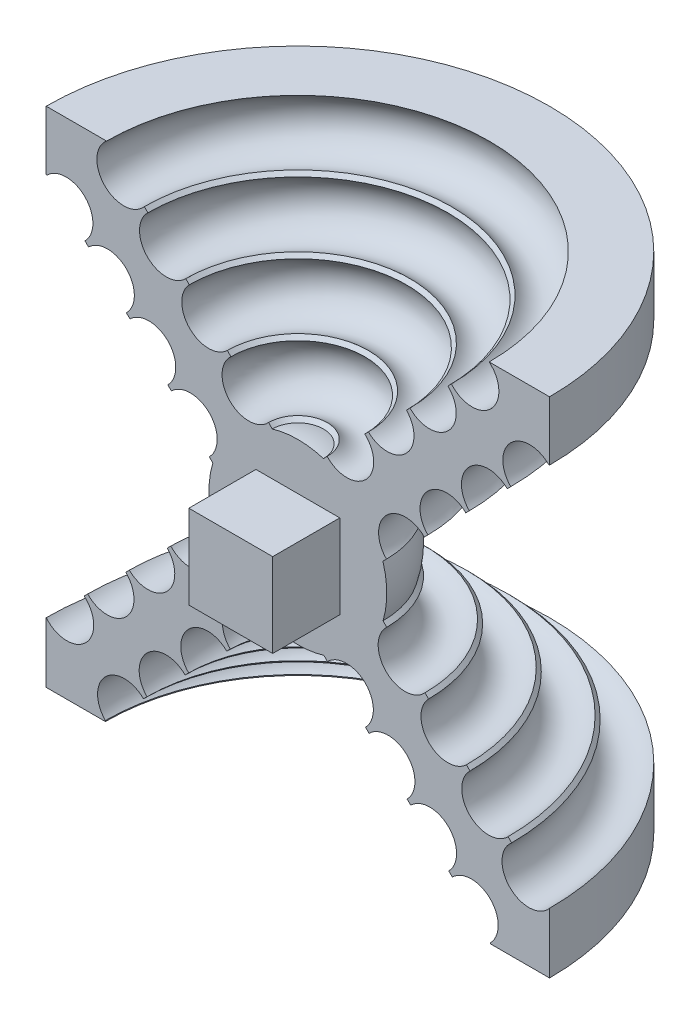
SolidWorks part; units mm, degrees
ref_plane "Front Plane" through (0, 0, 0) normal (0, 0, 1) x (1, 0, 0)
ref_plane "Top Plane" through (0, 0, 0) normal (0, 1, 0) x (1, 0, 0)
ref_plane "Right Plane" through (0, 0, 0) normal (1, 0, 0) x (0, 0, -1)
sketch "Sketch1" plane through (0, 0, 0) normal (0, 0, 1) x (1, 0, 0)
  line L42 (-19.05, 14.5706) -> (-19.05, 19.05) construction
  line L43 (-19.05, 19.05) -> (-14.4798, 19.05) construction
  line L46 (-18.9806, 14.5706) -> (-19.05, 14.5706)
  line L51 (1.9692, 6.4365) -> (2.2383, 6.7071)
  line L52 (6.4458, 1.9385) -> (6.727, 2.2183)
  line L66 (-6.4365, 1.9692) -> (-6.7071, 2.2383)
  line L67 (5.1188, 9.5739) -> (5.3889, 9.8426)
  line L68 (9.6188, 5.068) -> (9.8917, 5.3396)
  line L69 (-1.9385, 6.4458) -> (-2.2183, 6.727)
  line L70 (8.2694, 12.7095) -> (8.5395, 12.9782)
  line L71 (0, 19.05) -> (0, 0) construction
  line L72 (12.7597, 8.2194) -> (13.0295, 8.488)
  line L73 (11.42, 15.845) -> (11.6901, 16.1138)
  line L74 (15.91, 11.3547) -> (16.1804, 11.6238)
  line L75 (14.5706, 19.05) -> (19.05, 19.05)
  line L76 (19.05, 19.05) -> (19.05, 14.4798)
  line L77 (6.4365, -1.9692) -> (6.7071, -2.2383)
  line L78 (1.9385, -6.4458) -> (2.2183, -6.727)
  line L79 (19.05, -19.05) -> (-19.05, -19.05) construction
  line L80 (19.05, -19.05) -> (19.05, 19.05) construction
  line L81 (19.05, 19.05) -> (-19.05, 19.05) construction
  line L82 (-19.05, -19.05) -> (-19.05, 19.05) construction
  line L83 (9.5739, -5.1188) -> (9.8426, -5.3889)
  line L84 (5.068, -9.6188) -> (5.3396, -9.8917)
  line L85 (12.7095, -8.2694) -> (12.9782, -8.5395)
  line L86 (8.2194, -12.7597) -> (8.488, -13.0295)
  line L87 (15.845, -11.42) -> (16.1138, -11.6901)
  line L88 (11.3547, -15.91) -> (11.6238, -16.1804)
  line L89 (19.05, -14.5706) -> (19.05, -19.05)
  line L90 (-19.05, 14.5706) -> (-19.05, 19.05)
  line L91 (-19.05, 19.05) -> (-14.4798, 19.05)
  line L92 (19.05, -19.05) -> (14.4798, -19.05)
  line L93 (-1.9692, -6.4365) -> (-2.2383, -6.7071)
  line L94 (-15.845, 11.42) -> (-16.1138, 11.6901)
  line L95 (-12.7095, 8.2694) -> (-12.9782, 8.5395)
  line L96 (-9.5739, 5.1188) -> (-9.8426, 5.3889)
  line L97 (-5.068, 9.6188) -> (-5.3396, 9.8917)
  line L98 (-8.2194, 12.7597) -> (-8.488, 13.0295)
  line L99 (-11.3547, 15.91) -> (-11.6238, 16.1804)
  line L100 (-6.4458, -1.9385) -> (-6.727, -2.2183)
  line L101 (-5.1188, -9.5739) -> (-5.3889, -9.8426)
  line L102 (-9.6188, -5.068) -> (-9.8917, -5.3396)
  line L103 (-8.2694, -12.7095) -> (-8.5395, -12.9782)
  line L104 (-12.7597, -8.2194) -> (-13.0295, -8.488)
  line L105 (-11.42, -15.845) -> (-11.6901, -16.1138)
  line L106 (-15.91, -11.3547) -> (-16.1804, -11.6238)
  line L107 (-14.5706, -19.05) -> (-19.05, -19.05)
  line L108 (-19.05, -19.05) -> (-19.05, -14.4798)
  line L109 (0, 6.731) -> (0, -6.731)
  line L110 (14.5706, 18.9806) -> (14.5706, 19.05)
  line L111 (18.9806, -14.5706) -> (19.05, -14.5706)
  line L112 (-14.5706, -18.9806) -> (-14.5706, -19.05)
  line L114 (3.175, -3.175) -> (-3.175, -3.175) construction
  line L115 (3.175, -3.175) -> (3.175, 3.175) construction
  line L116 (3.175, 3.175) -> (-3.175, 3.175) construction
  line L117 (-3.175, -3.175) -> (-3.175, 3.175) construction
  line L118 (3.175, -3.175) -> (-3.175, 3.175) construction
  line L119 (3.175, 3.175) -> (-3.175, -3.175) construction
  arc A0 (-18.9806, 14.5706) -> (-16.1138, 11.6901) centre (-17.5472, 13.1303) cw
  arc A4 (-15.845, 11.42) -> (-12.9782, 8.5395) centre (-14.4116, 9.9798) cw
  arc A5 (-12.7095, 8.2694) -> (-9.8426, 5.3889) centre (-11.2761, 6.8292) cw
  arc A6 (-9.5739, 5.1188) -> (-6.7071, 2.2383) centre (-8.1405, 3.6786) cw
  arc A7 (-6.4365, 1.9692) -> (-6.4458, -1.9385) centre (0, 0) ccw
  arc A8 (-5.068, 9.6188) -> (-2.2183, 6.727) centre (-3.7075, 8.1095) ccw
  arc A9 (-8.2194, 12.7597) -> (-5.3396, 9.8917) centre (-6.755, 11.3503) ccw
  arc A10 (-11.3547, 15.91) -> (-8.488, 13.0295) centre (-9.954, 14.4373) ccw
  arc A11 (-14.4798, 19.05) -> (-11.6238, 16.1804) centre (-13.1814, 17.4862) ccw
  arc A12 (9.6188, 5.068) -> (6.727, 2.2183) centre (8.1095, 3.7075) ccw
  arc A13 (5.1188, 9.5739) -> (2.2383, 6.7071) centre (3.6786, 8.1405) cw
  arc A14 (12.7597, 8.2194) -> (9.8917, 5.3396) centre (11.3503, 6.755) ccw
  arc A15 (8.2694, 12.7095) -> (5.3889, 9.8426) centre (6.8292, 11.2761) cw
  arc A16 (15.91, 11.3547) -> (13.0295, 8.488) centre (14.4373, 9.954) ccw
  arc A17 (11.42, 15.845) -> (8.5395, 12.9782) centre (9.9798, 14.4116) cw
  arc A18 (19.05, 14.4798) -> (16.1804, 11.6238) centre (17.4862, 13.1814) ccw
  arc A19 (14.5706, 18.9806) -> (11.6901, 16.1138) centre (13.1303, 17.5472) cw
  arc A20 (5.068, -9.6188) -> (2.2183, -6.727) centre (3.7075, -8.1095) ccw
  arc A21 (9.5739, -5.1188) -> (6.7071, -2.2383) centre (8.1405, -3.6786) cw
  arc A22 (8.2194, -12.7597) -> (5.3396, -9.8917) centre (6.755, -11.3503) ccw
  arc A23 (12.7095, -8.2694) -> (9.8426, -5.3889) centre (11.2761, -6.8292) cw
  arc A24 (11.3547, -15.91) -> (8.488, -13.0295) centre (9.954, -14.4373) ccw
  arc A25 (15.845, -11.42) -> (12.9782, -8.5395) centre (14.4116, -9.9798) cw
  arc A26 (14.4798, -19.05) -> (11.6238, -16.1804) centre (13.1814, -17.4862) ccw
  arc A27 (18.9806, -14.5706) -> (16.1138, -11.6901) centre (17.5472, -13.1303) cw
  arc A28 (-9.6188, -5.068) -> (-6.727, -2.2183) centre (-8.1095, -3.7075) ccw
  arc A29 (-5.1188, -9.5739) -> (-2.2383, -6.7071) centre (-3.6786, -8.1405) cw
  arc A30 (-12.7597, -8.2194) -> (-9.8917, -5.3396) centre (-11.3503, -6.755) ccw
  arc A31 (-8.2694, -12.7095) -> (-5.3889, -9.8426) centre (-6.8292, -11.2761) cw
  arc A32 (-15.91, -11.3547) -> (-13.0295, -8.488) centre (-14.4373, -9.954) ccw
  arc A33 (-11.42, -15.845) -> (-8.5395, -12.9782) centre (-9.9798, -14.4116) cw
  arc A34 (-19.05, -14.4798) -> (-16.1804, -11.6238) centre (-17.4862, -13.1814) ccw
  arc A35 (-14.5706, -18.9806) -> (-11.6901, -16.1138) centre (-13.1303, -17.5472) cw
  arc A36 (-4.7625, -4.7566) -> (-4.7506, -4.7684) centre (0, 0) ccw
  arc A37 (-1.9692, -6.4365) -> (-1.9385, 6.4458) centre (0, 0) ccw
  point P0 (0, 0)
  point P2 (-2.0784, 6.5864)
  point P5 (0.003, -0.003)
  point P12 (0, 0)
  point P13 (0, 0)
  point P47 (-5.2038, 9.7552)
  point P131 (0, 0)
  dimension "D10" = 4
  dimension "D5" = 13.462
  dimension "D11" = 2.032
  dimension "D12" = 14.4116
  dimension "D13" = 0.3967
  dimension "D14" = 3.173
  dimension "D15" = 3.1422
  dimension "D8" = 4.5702
  dimension "D20" = 0.0803
  dimension "D19" = 0.0105
  dimension "D21" = 2.032
  dimension "D9" = 0.3816
  dimension "D16" = 2.032
  dimension "D23" = 19.05
  dimension "D27" = 2.0325
  dimension "D32" = 2.0325
  dimension "D33" = 2.0325
  dimension "D35" = 21.8979
  dimension "D3" = 3.1931
  dimension "D4" = 38.1
  dimension "D6" = 6.35
  dimension "D7" = 4.4794
  dimension "D17" = 6.5864
  dimension "D18" = 6.7071
  dimension "D24" = 2.2243
  dimension "D22" = 0.381
  dimension "D25" = 0.0257
  dimension "D26" = 0.385
  dimension "D28" = 0.3807
  dimension "D29" = 0.0438
  dimension "D30" = 0.0461
  dimension "D31" = 3.175
  dimension "D34" = 19.05
  dimension "D37" = 4
  dimension "D36" = 4
revolve "Sphericon Revolve" add sketch "Sketch1" angle 180 about L71 region at (-19.0153, 14.9966, 0)
sketch "Sketch2" plane through (0, 0, 0) normal (0, 0, 1) x (1, 0, 0)
  line L1 (-3.175, -3.175) -> (3.175, -3.175)
  line L2 (-3.175, -3.175) -> (-3.175, 3.175)
  line L3 (-3.175, 3.175) -> (3.175, 3.175)
  line L4 (3.175, -3.175) -> (3.175, 3.175)
  line L5 (-3.175, -3.175) -> (3.175, 3.175) construction
  line L6 (-3.175, 3.175) -> (3.175, -3.175) construction
  point P0 (0, 0)
  dimension "D1" = 6.35
  dimension "D2" = 6.35
extrude "Male Extrude" add sketch "Sketch2" along normal blind 5.08
